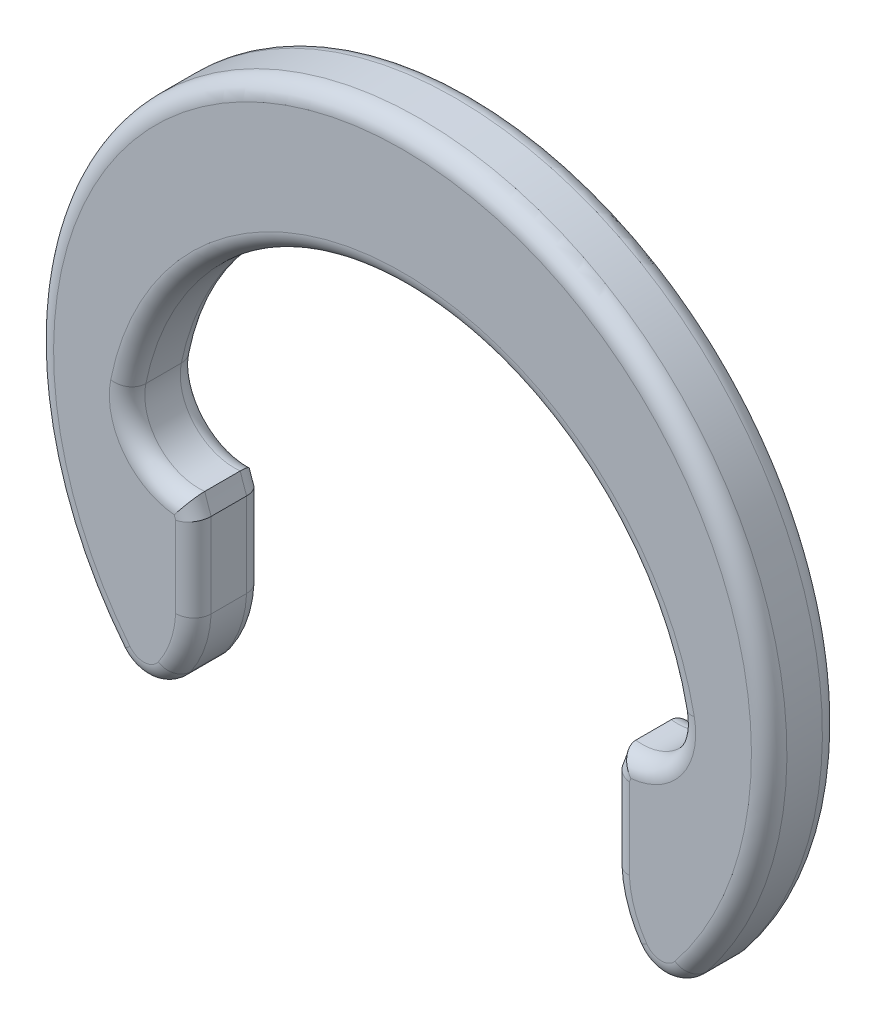
SolidWorks part; units mm, degrees
ref_plane "Front" through (0, 0, 0) normal (0, 0, 1) x (1, 0, 0)
ref_plane "Top" through (0, 0, 0) normal (0, 1, 0) x (1, 0, 0)
ref_plane "Right" through (0, 0, 0) normal (1, 0, 0) x (0, 0, -1)
sketch "Sketch1" plane through (0, 0, 0) normal (0, 0, 1) x (1, 0, 0)
  line L0 (0, 3.1) -> (0, -3.1) construction
  line L1 (-1.9, 0) -> (-3.1, 0) construction
  line L2 (-2.5, 0) -> (-1.9, 0) construction
  line L3 (-1.9, 0) -> (1.9, 0) construction
  line L4 (-1.7678, -1.7678) -> (-1.7678, -0.6964) construction
  line L5 (-1.8216, -0.54) -> (1.8216, -0.54) construction
  line L6 (-1.9, 0) -> (-1.9, -0.54) construction
  line L7 (0, 0) -> (-1.3435, -1.3435) construction
  line L8 (-1.3435, -1.3435) -> (-2.192, -2.192) construction
  circle A0 centre (0, 0) radius 3.1 construction
  circle A1 centre (0, 0) radius 1.9 construction
  arc A2 (0, 1.9) -> (-2.32, 0) centre (0, -0.4664) ccw construction
  arc A5 (-1.8216, -0.54) -> (-2.32, 0) centre (-1.8752, -0.0894) cw construction
  point P21 (0, 1.9)
  point P23 (0, 3.1)
  dimension "Ring OD" = 6.2
  dimension "D3" = 3.8
  dimension "Max Section" = 1.2
  dimension "D1" = 45
  dimension "D2" = 0.78
  dimension "D4" = 0.54
sketch "Sketch3" plane through (0, 0, 0) normal (0, 1, 0) x (1, 0, 0)
  line L0 (-3.1, 0.3) -> (-3.1, -0.3) construction
  line L3 (-1.9, 0) -> (-3.1, 0) construction
  point P3 (-3.1, 0)
  dimension "Ring Thickness" = 0.6
sketch "Sketch2" plane through (0, 0, 0) normal (0, 0, 1) x (1, 0, 0)
  line L0 (-1.7678, -1.7678) -> (-1.7678, -1.4107) construction
  line L1 (-1.7678, -1.4107) -> (-1.7678, -1.0535)
  line L2 (-1.7678, -1.0535) -> (-1.7678, -0.6964)
  line L3 (0, 1.9) -> (0, 0) construction
  line L4 (0, 3.1) -> (0, -3.1) construction
  line L5 (-1.7678, -1.7678) -> (-1.9092, -1.9092) construction
  line L6 (0, 3.1) -> (0, 1.9) construction
  line L7 (-1.9092, -1.9092) -> (-2.0506, -2.0506) construction
  line L8 (-2.0506, -2.0506) -> (-2.192, -2.192)
  line L9 (-1.3435, -1.3435) -> (-2.192, -2.192) construction
  line L10 (1.7678, -1.0535) -> (1.7678, -0.6964)
  line L11 (1.7678, -1.4107) -> (1.7678, -1.0535)
  line L12 (2.0506, -2.0506) -> (2.192, -2.192)
  circle A0 centre (0, 0) radius 3.1 construction
  arc A1 (0, 1.9) -> (-2.32, 0) centre (0, -0.4664) ccw construction
  circle A3 centre (0, 0) radius 1.9 construction
  arc A4 (2.192, -2.192) -> (-2.192, -2.192) centre (0, 0) ccw
  arc A5 (2.32, 0) -> (-2.32, 0) centre (0, -0.4664) ccw
  arc A6 (-2.32, 0) -> (-1.8216, -0.54) centre (-1.8752, -0.0894) ccw construction
  arc A7 (-1.8216, -0.54) -> (-1.7678, -0.6964) centre (0, 0) ccw
  arc A8 (-1.7678, -1.4107) -> (-2.0506, -2.0506) centre (-2.736, -1.3652) cw
  arc A9 (1.7678, -1.4107) -> (2.0506, -2.0506) centre (2.736, -1.3652) ccw
  arc A10 (1.8216, -0.54) -> (1.7678, -0.6964) centre (0, 0) cw
  arc A11 (2.32, 0) -> (1.8216, -0.54) centre (1.8752, -0.0894) cw
  arc A12 (-2.32, 0) -> (-1.8216, -0.54) centre (-1.8752, -0.0894) ccw
extrude "Boss-Extrude1" add sketch "Sketch2" along normal mid plane 0.6
fillet "Fillet1" radius 0.3 2 edges at (2.192, -2.192, 0) (-2.192, -2.192, 0)
fillet "Fillet2" radius 0.15 24 edges at (-2.1774, -2.0481, -0.3) (-1.8184, -1.6776, -0.3) (-1.7678, -1.0535, -0.3) (-1.7964, -0.6188, -0.3) (-2.2086, -0.3972, -0.3) (0, 1.9, -0.3) (2.2086, -0.3972, -0.3) (1.7964, -0.6188, -0.3) (1.7678, -1.0535, -0.3) (1.8184, -1.6776, -0.3) (2.1774, -2.0481, -0.3) (0, 3.1, -0.3) (1.7678, -1.0535, 0.3) (1.7964, -0.6188, 0.3) (2.2086, -0.3972, 0.3) (0, 1.9, 0.3) (-2.2086, -0.3972, 0.3) (-1.7964, -0.6188, 0.3) (-1.7678, -1.0535, 0.3) (-1.8184, -1.6776, 0.3) (-2.1774, -2.0481, 0.3) (0, 3.1, 0.3) (2.1774, -2.0481, 0.3) (1.8184, -1.6776, 0.3)
ref_axis "Center Axis 1" through (0, 0, 0.15) along (0, 0, -1)
ref_plane "Contact Plane 1" through (0, 0, 0.3) normal (0, 0, 1) x (1, 0, 0)
ref_plane "Contact Plane 2" through (0, 0, -0.3) normal (0, 0, -1) x (-1, 0, 0)
equation "\"D1@Boss-Extrude1\"=\"Ring Thickness@Sketch3\""
equation "\"D1@Fillet1\" = \"Max Section@Sketch1\" / 4"
equation "\"D2@Sketch1\"=\"Max Section@Sketch1\"*.65"
equation "\"D4@Sketch1\"=\"Max Section@Sketch1\"*.45"
equation "\"D1@Fillet2\"=\"Ring Thickness@Sketch3\"/4"
